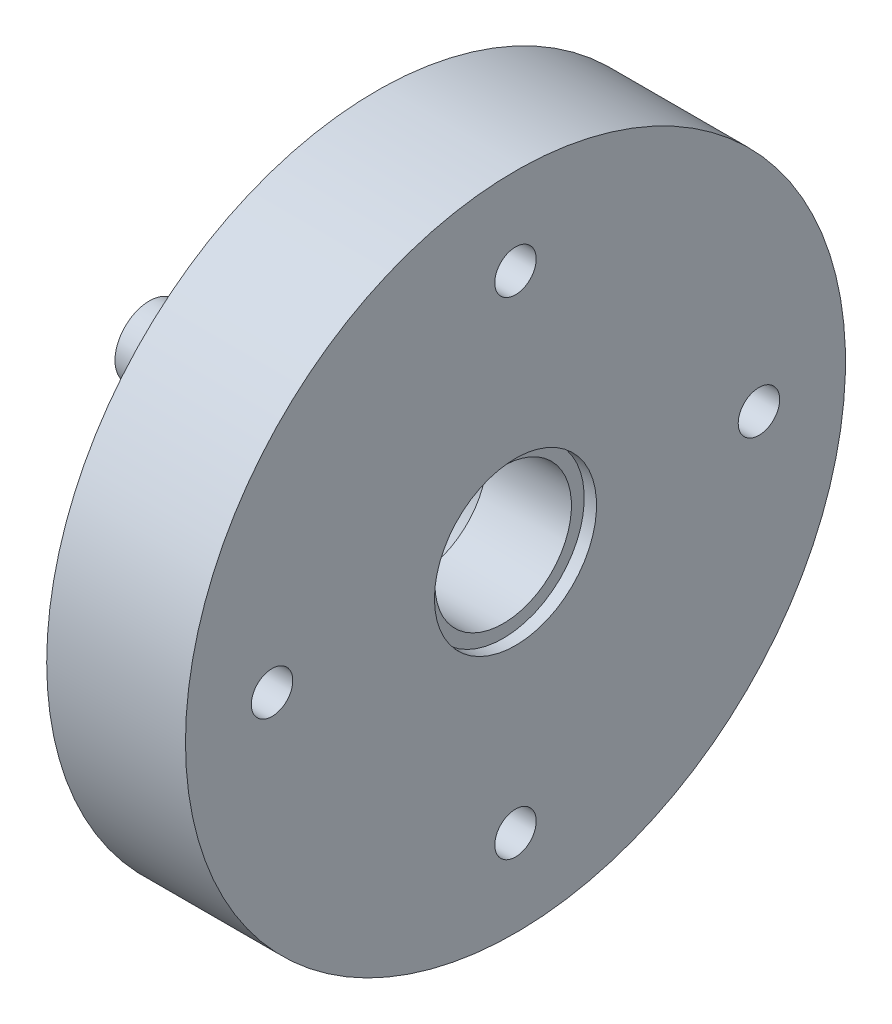
SolidWorks part; units mm, degrees
ref_plane "Front Plane" through (0, 0, 0) normal (0, 0, 1) x (1, 0, 0)
ref_plane "Top Plane" through (0, 0, 0) normal (0, 1, 0) x (1, 0, 0)
ref_plane "Right Plane" through (0, 0, 0) normal (1, 0, 0) x (0, 0, -1)
sketch "Sketch1" plane through (0, 0, 0) normal (0, 0, 1) x (1, 0, 0)
  line L0 (-795.1638, 11.7142) -> (36114.285, 11.7142) construction
  line L3 (-71.2919, 14.8842) -> (-71.2919, 14.5342)
  line L8 (-75.7419, 13.3992) -> (-59.4889, 13.3992)
  line L9 (-75.7419, 13.3992) -> (-75.7419, 14.5342)
  line L10 (-45.7058, 19.9775) -> (-45.7058, 38.788)
  line L12 (-45.7058, 38.788) -> (-57.0912, 38.788)
  line L13 (-62.3716, 14.5342) -> (-59.4889, 23.788)
  line L15 (-45.7058, 19.9775) -> (-45.7058, 18.3642)
  line L16 (-45.7058, 18.3642) -> (-46.7158, 18.3642)
  line L17 (-46.7158, 18.3642) -> (-46.7158, 17.3142)
  line L18 (-57.0912, 38.788) -> (-57.0912, 23.788)
  line L19 (-59.4889, 23.788) -> (-57.0912, 23.788)
  line L20 (-59.4889, 13.3992) -> (-53.6375, 17.3142)
  line L21 (-75.7419, 14.5342) -> (-71.2919, 14.8842)
  line L22 (-53.6375, 17.3142) -> (-46.7158, 17.3142)
  line L23 (-71.2919, 14.5342) -> (-66.8419, 14.8842)
  line L26 (-66.8419, 14.8842) -> (-66.8419, 14.5342)
  line L27 (-66.8419, 14.5342) -> (-62.3716, 14.8842)
  line L28 (-62.3716, 14.8842) -> (-62.3716, 14.5342)
  dimension "D1" = 13.3
  dimension "D5" = 11.2
  dimension "D2" = 6.34
  dimension "D3" = 1.01
  dimension "D4" = 15
  dimension "D6" = 3.37
  dimension "D7" = 5.64
revolve "Revolve17" add sketch "Sketch1" angle 360 about L0
sketch "Sketch3" plane through (-57.0912, 0, 0) normal (-1, 0, 0) x (0, 0, 1)
  circle A2 centre (0, 11.7142) radius 19.9711 construction
  point P2 (0, 31.6853)
  point P3 (19.9711, 11.7142)
  point P4 (0, -8.2569)
  point P6 (-19.9711, 11.7142)
hole_wizard "CBORE for M3 Hex Socket Head Cap Screw1" positions "Sketch3" profile "Sketch4" counterbore size "M3" standard "ISO" end condition through all
sketch "Sketch4" plane through (-57.0912, 11.7142, -19.9711) normal (0, 1, 0) x (0, 0, 1)
  line L0 (0, 0) -> (0, 11.3854)
  line L1 (0, 11.3854) -> (1.7, 11.3854)
  line L3 (1.7, 11.3854) -> (1.7, 3.4)
  line L4 (3.25, 3.4) -> (1.7, 3.4)
  line L5 (3.25, 3.4) -> (3.25, 0.025)
  line L6 (3.25, 0.025) -> (3.275, 0)
  line L7 (3.275, 0) -> (0, 0)
  line L8 (-3.25, 0.025) -> (-3.275, 0) construction
  line L11 (0, -6.35) -> (0, 107.95) construction
  dimension "Thru Hole Dia." = 3.4
  dimension "Thru Hole Depth" = 11.3854
  dimension "C'Bore Dia." = 6.5
  dimension "C'Bore Depth" = 3.4
  dimension "Near C'Sink Dia." = 6.55
  dimension "Near C'Sink Angle" = 90
